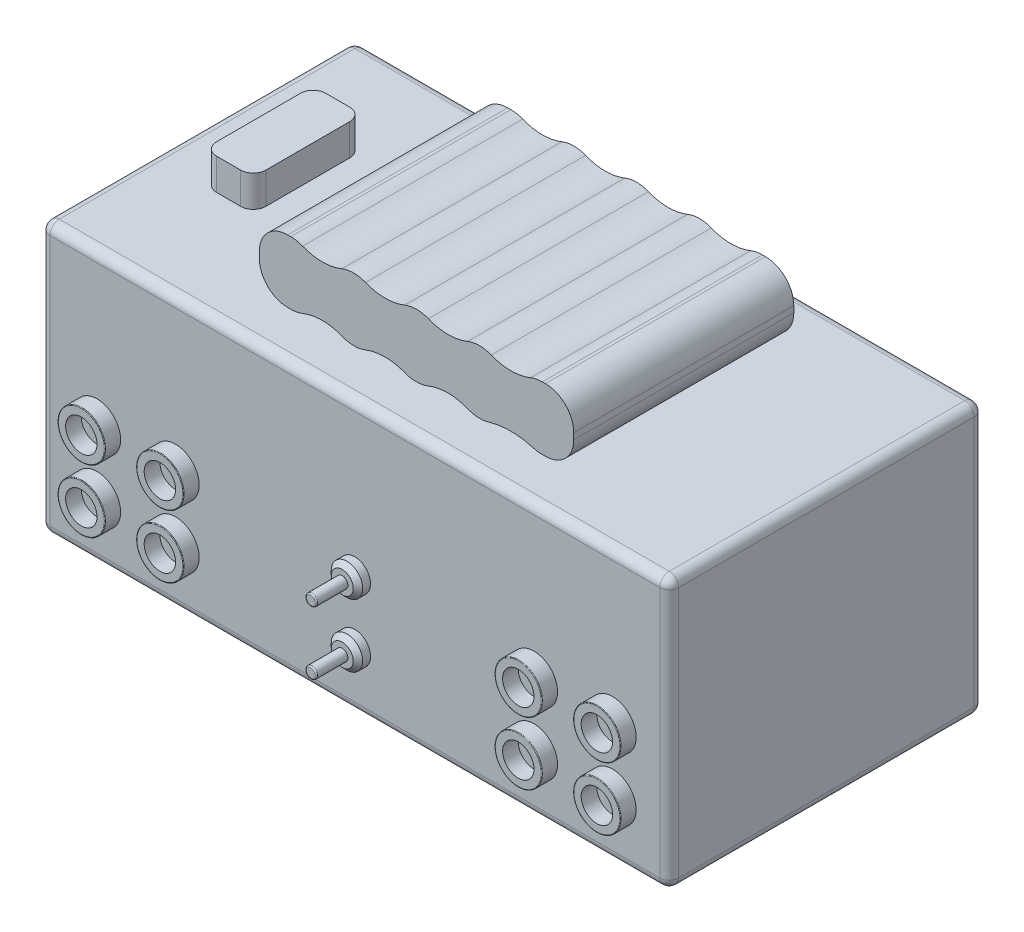
SolidWorks part; units mm, degrees
note: The reader was unsure of these and kept them because the rebuilt part matched: shared geometry of "Sketch5<3>", "Sketch10<4>", "Sketch10<5>", "Sketch10<8>", "Sketch10<9>".
ref_plane "Front Plane" through (0, 0, 0) normal (0, 0, 1) x (1, 0, 0)
ref_plane "Top Plane" through (0, 0, 0) normal (0, 1, 0) x (1, 0, 0)
ref_plane "Right Plane" through (0, 0, 0) normal (1, 0, 0) x (0, 0, -1)
sketch "Sketch2" plane through (0, 0, 0) normal (0, 1, 0) x (1, 0, 0)
  line L1 (0, 0) -> (127, 0)
  line L2 (0, 0) -> (0, 63.5)
  line L3 (0, 63.5) -> (127, 63.5)
  line L4 (127, 0) -> (127, 63.5)
  dimension "D1" = 63.5
  dimension "D2" = 127
extrude "Boss-Extrude1" add sketch "Sketch2" along normal blind 54.61
fillet "Fillet1" radius 1.905 12 edges at (0, 27.305, -63.5) (0, 0, -31.75) (63.5, 0, -63.5) (0, 54.61, -31.75) (63.5, 54.61, -63.5) (127, 54.61, -31.75) (127, 27.305, -63.5) (127, 0, -31.75) (127, 27.305, 0) (63.5, 0, 0) (0, 27.305, 0) (63.5, 54.61, 0)
sketch "Sketch3" plane through (0, 0, 0) normal (0, 0, 1) x (1, 0, 0)
  line L0 (1.905, 1.905) -> (11.43, 1.905)
  line L1 (1.905, 1.905) -> (125.095, 1.905) construction
  circle A0 centre (11.43, 11.43) radius 4.7625
  circle A1 centre (11.43, 11.43) radius 3.175
  circle A2 centre (11.43, 24.13) radius 4.7625
  circle A3 centre (11.43, 24.13) radius 3.175
  circle A4 centre (27.305, 24.13) radius 4.7625
  circle A5 centre (27.305, 24.13) radius 3.175
  circle A6 centre (27.305, 11.43) radius 4.7625
  circle A7 centre (27.305, 11.43) radius 3.175
  circle A8 centre (99.695, 24.13) radius 3.175
  circle A9 centre (99.695, 24.13) radius 4.7625
  circle A10 centre (99.695, 11.43) radius 3.175
  circle A11 centre (99.695, 11.43) radius 4.7625
  circle A12 centre (115.57, 11.43) radius 3.175
  circle A13 centre (115.57, 11.43) radius 4.7625
  circle A14 centre (115.57, 24.13) radius 3.175
  circle A15 centre (115.57, 24.13) radius 4.7625
extrude "Boss-Extrude2" add sketch "Sketch3" along normal blind 3.175 contours A2 A3 | A4 A5 | A6 A7 | A0 A1 | A11 A10 | A9 A8 | A15 A14 | A13 A12
fillet "Fillet2" radius 0.127 8 edges at (104.4575, 11.43, 3.175) (120.3325, 11.43, 3.175) (120.3325, 24.13, 3.175) (104.4575, 24.13, 3.175) (32.0675, 11.43, 3.175) (16.1925, 11.43, 3.175) (32.0675, 24.13, 3.175) (16.1925, 24.13, 3.175)
sketch "Sketch5" plane through (0, 0, 0) normal (0, 0, 1) x (1, 0, 0)
  line L0 (92.4825, 54.61) -> (40.4125, 54.61)
  line L1 (1.905, 54.61) -> (125.095, 54.61) construction
  line L5 (98.1975, 60.325) -> (98.1975, 61.595)
  line L6 (92.4825, 67.31) -> (40.4125, 67.31)
  line L7 (34.6975, 61.595) -> (34.6975, 60.325)
  arc A0 (98.1975, 61.595) -> (92.4825, 67.31) centre (92.4825, 61.595) ccw
  arc A1 (98.1975, 60.325) -> (92.4825, 54.61) centre (92.4825, 60.325) cw
  arc A2 (40.4125, 54.61) -> (34.6975, 60.325) centre (40.4125, 60.325) cw
  arc A3 (34.6975, 61.595) -> (40.4125, 67.31) centre (40.4125, 61.595) cw
  point P7 (98.1975, 54.61)
  point P10 (34.6975, 54.61)
  point P12 (34.6975, 54.61)
  point P13 (98.1975, 54.61)
  dimension "D1" = 5.715
extrude "Boss-Extrude3" add sketch "Sketch5" against normal blind 53.975
extrude "Cut-Extrude1" cut sketch "Sketch5<3>" against normal blind 9.525
sketch "Sketch5<3>" plane through (0, 0, 0) normal (0, 0, 1) x (1, 0, 0) same geometry as "Sketch5"
sketch "Sketch6" plane through (0, 54.61, 0) normal (0, 1, 0) x (1, 0, 0)
  line L1 (13.1342, 44.4872) -> (17.986, 44.4872)
  line L2 (10.5942, 41.9472) -> (10.5942, 24.999)
  line L3 (13.1342, 22.459) -> (17.986, 22.459)
  line L4 (20.526, 41.9472) -> (20.526, 24.999)
  arc A0 (10.5942, 24.999) -> (13.1342, 22.459) centre (13.1342, 24.999) ccw
  arc A1 (20.526, 24.999) -> (17.986, 22.459) centre (17.986, 24.999) cw
  arc A2 (20.526, 41.9472) -> (17.986, 44.4872) centre (17.986, 41.9472) ccw
  arc A3 (13.1342, 44.4872) -> (10.5942, 41.9472) centre (13.1342, 41.9472) ccw
  dimension "D1" = 2.54
extrude "Boss-Extrude4" add sketch "Sketch6" along normal blind 6.35
sketch "Sketch7" plane through (0, 0, 0) normal (0, 0, 1) x (1, 0, 0)
  line L0 (27.305, 11.43) -> (99.695, 11.43)
  line L1 (27.305, 24.13) -> (99.695, 24.13)
  circle A0 centre (63.5, 24.13) radius 3.175
  circle A1 centre (63.5, 11.43) radius 3.175
extrude "Boss-Extrude5" add sketch "Sketch7" along normal blind 2.54 contours L1 A0 | L1 A0 | L0 A1 | L0 A1
chamfer "Chamfer2" distance 0.9525 angle 45 2 edges at (66.675, 11.43, 2.54) (66.675, 24.13, 2.54)
sketch "Sketch8" plane through (0, 0, 2.54) normal (0, 0, 1) x (1, 0, 0)
  circle A0 centre (63.5, 24.13) radius 1.143
  circle A1 centre (63.5, 11.43) radius 1.143
extrude "Boss-Extrude6" add sketch "Sketch8" along normal blind 6.35
fillet "Fillet3" radius 0.254 2 edges at (64.643, 24.13, 8.89) (64.643, 11.43, 8.89)
sketch "Sketch10" plane through (0, 0, -9.525) normal (0, 0, 1) x (1, 0, 0)
  line L0 (34.6975, 60.96) -> (41.0475, 60.96)
  line L1 (34.6975, 61.595) -> (34.6975, 60.325) construction
  line L2 (40.4125, 54.61) -> (92.4825, 54.61) construction
  line L3 (60.0975, 55.7866) -> (60.0975, 55.2974)
  line L4 (85.4742, 55.5118) -> (85.4742, 55.2974)
  circle A0 centre (41.0475, 60.96) radius 6.35
  circle A1 centre (53.7475, 60.96) radius 6.35
  circle A2 centre (66.4475, 60.96) radius 6.35
  circle A3 centre (79.1475, 60.96) radius 6.35
  circle A4 centre (91.8475, 60.96) radius 6.35
  arc A5 (43.432, 66.8453) -> (51.363, 66.8453) centre (47.3975, 76.6328) ccw
  arc A6 (56.132, 66.8453) -> (64.063, 66.8453) centre (60.0975, 76.6328) ccw
  arc A7 (68.832, 66.8453) -> (76.763, 66.8453) centre (72.7975, 76.6328) ccw
  arc A8 (81.532, 66.8453) -> (89.463, 66.8453) centre (85.4975, 76.6328) ccw
  arc A9 (64.1175, 55.0256) -> (65.7984, 54.61) centre (66.3655, 60.51) ccw
  arc A10 (68.832, 55.0747) -> (76.763, 55.0747) centre (72.7975, 45.2872) cw
  arc A11 (56.0776, 55.0256) -> (54.3967, 54.61) centre (53.8296, 60.51) cw
  arc A12 (43.432, 55.0747) -> (51.363, 55.0747) centre (47.3975, 45.2872) cw
  arc A13 (56.0776, 55.0256) -> (64.1175, 55.0256) centre (60.0975, 44.7873) cw
  arc A14 (80.9709, 54.8507) -> (89.9794, 54.864) centre (85.4975, 39.6853) cw
  arc A15 (89.9794, 54.864) -> (91.3228, 54.61) centre (91.9132, 61.4133) ccw
  arc A16 (80.9709, 54.8507) -> (79.7465, 54.61) centre (78.8853, 62.2251) cw
  dimension "D1" = 6.35
  dimension "D2" = 5
  dimension "D3" = 4
extrude "Cut-Extrude10" cut sketch "Sketch10" against normal blind 76.2 contours A0 A5 A1 A4 | A1 A6 A2 A4 | A2 A7 A3 A4 | A3 A8 A4
extrude "Cut-Extrude12" cut sketch "Sketch10<4>" against normal blind 76.2 contours A12 A0 A8 A1
sketch "Sketch10<4>" plane through (0, 0, -9.525) normal (0, 0, 1) x (1, 0, 0) same geometry as "Sketch10"
extrude "Cut-Extrude14" cut sketch "Sketch10<5>" against normal blind 76.2 contours A10 A2 A8 A3
sketch "Sketch10<5>" plane through (0, 0, -9.525) normal (0, 0, 1) x (1, 0, 0) same geometry as "Sketch10"
extrude "Cut-Extrude18" cut sketch "Sketch10<8>" against normal blind 76.2
sketch "Sketch10<8>" plane through (0, 0, -9.525) normal (0, 0, 1) x (1, 0, 0) same geometry as "Sketch10"
extrude "Cut-Extrude19" cut sketch "Sketch10<9>" against normal blind 76.2
sketch "Sketch10<9>" plane through (0, 0, -9.525) normal (0, 0, 1) x (1, 0, 0) same geometry as "Sketch10"
